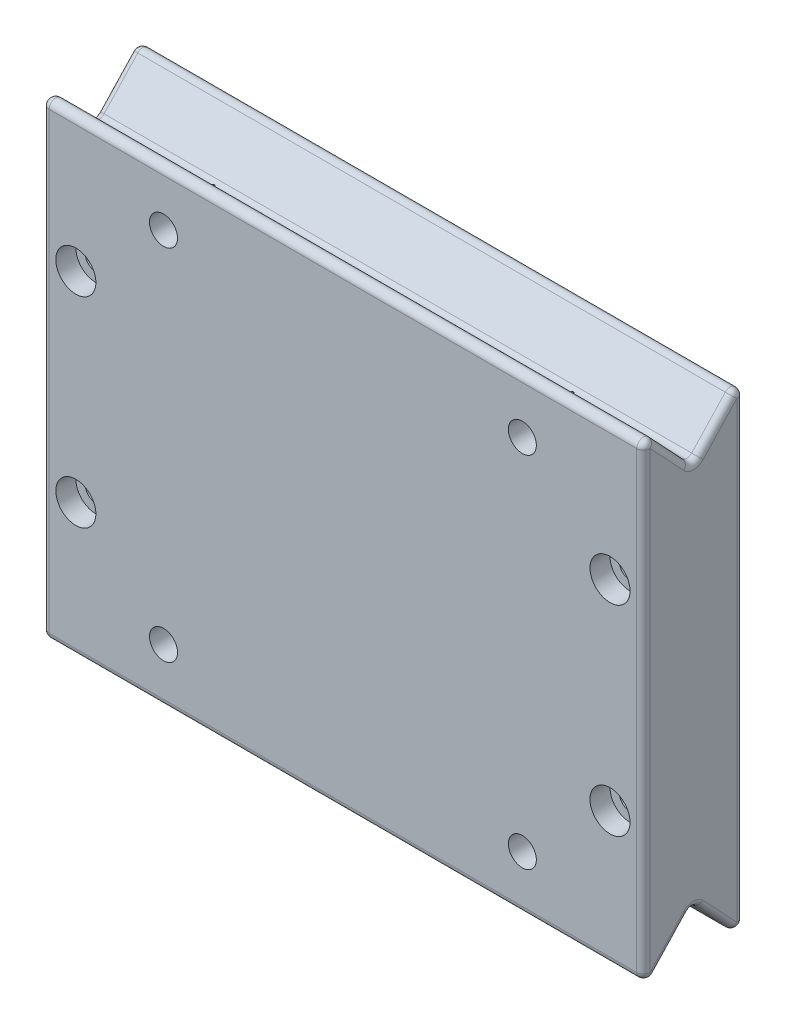
SolidWorks part; units mm, degrees
ref_plane "前视基准面" through (0, 0, 0) normal (0, 0, 1) x (1, 0, 0)
ref_plane "上视基准面" through (0, 0, 0) normal (0, 1, 0) x (1, 0, 0)
ref_plane "右视基准面" through (0, 0, 0) normal (1, 0, 0) x (0, 0, -1)
other "Configuration Table"
sketch "草图1" plane through (0, 0, 0) normal (0, 0, 1) x (1, 0, 0)
  line L0 (0, 0) -> (0, 22500.8852) construction
  line L1 (0, 0) -> (22500.8852, 0) construction
  line L3 (-45, 36.5) -> (45, 36.5)
  line L4 (-45, 36.5) -> (-45, -36.5)
  line L5 (-45, -36.5) -> (45, -36.5)
  line L6 (45, 36.5) -> (45, -36.5)
  line L7 (-45, 36.5) -> (45, -36.5) construction
  line L8 (-45, -36.5) -> (45, 36.5) construction
  circle A0 centre (-26.87, 26.87) radius 2.1
  circle A1 centre (26.87, 26.87) radius 2.1
  circle A2 centre (26.87, -26.87) radius 2.1
  circle A3 centre (-26.87, -26.87) radius 2.1
  point P5 (0, 0)
  dimension "D3" = 53.74
  dimension "D4" = 53.74
  dimension "D5" = 4.2
  dimension "D1" = 90
  dimension "D2" = 73
extrude "凸台-拉伸1" add sketch "草图1" along normal blind 15
sketch "草图2" plane through (0, 0, 0) normal (0, 0, -1) x (-1, 0, 0)
  line L0 (0, 36.5) -> (0, -36.5) construction
  line L1 (45, 36.5) -> (-45, 36.5) construction
  line L2 (45, -36.5) -> (-45, -36.5) construction
  line L3 (-45, 0) -> (45, 0) construction
  line L4 (-45, 36.5) -> (-45, -36.5) construction
  line L5 (45, 36.5) -> (45, -36.5) construction
  circle A0 centre (-26.87, 26.87) radius 4.5
  circle A1 centre (26.87, 26.87) radius 4.5
  circle A2 centre (26.87, -26.87) radius 4.5
  circle A3 centre (-26.87, -26.87) radius 4.5
  dimension "D1" = 9
extrude "切除-拉伸1" cut sketch "草图2" against normal blind 3
sketch "草图5" plane through (-45, 0, 0) normal (-1, 0, 0) x (0, 0, 1)
  line L0 (0, 0) -> (15, 0) construction
  line L1 (15, 36.5) -> (15, -36.5) construction
  line L2 (7.5, 36.5) -> (7.5, -36.5) construction
  line L3 (15, 36.5) -> (0, 36.5) construction
  line L4 (15, -36.5) -> (0, -36.5) construction
  line L5 (0, 36.5) -> (7.5, 28.5)
  line L7 (15, 36.5) -> (0, 36.5)
  line L8 (0, -36.5) -> (7.5, -28.5)
  line L9 (7.5, -28.5) -> (15, -36.5)
  line L10 (15, -36.5) -> (0, -36.5)
  line L11 (7.5, 28.5) -> (15, 36.5)
  dimension "D1" = 8
  dimension "D2" = 8
extrude "切除-拉伸4" cut sketch "草图5" against normal through all
sketch "草图6" plane through (0, 0, 15) normal (0, 0, 1) x (1, 0, 0)
  line L0 (0, 0) -> (-50000, 0) construction
  line L1 (0, 0) -> (0, 50000) construction
  line L2 (-45, 36.5) -> (-45, -36.5) construction
  circle A0 centre (-40, 15) radius 1.6
  circle A1 centre (-40, -15) radius 1.6
  circle A2 centre (40, -15) radius 1.6
  circle A3 centre (40, 15) radius 1.6
  dimension "D1" = 15
  dimension "D2" = 5
  dimension "D3" = 3.2
extrude "切除-拉伸5" cut sketch "草图6" against normal through all
sketch "草图7" plane through (0, 0, 15) normal (0, 0, 1) x (1, 0, 0)
  line L0 (0, 36.5) -> (0, -36.5) construction
  line L1 (45, 36.5) -> (-45, 36.5) construction
  line L2 (-45, -36.5) -> (45, -36.5) construction
  line L3 (-45, 0) -> (45, 0) construction
  line L4 (-45, 36.5) -> (-45, -36.5) construction
  line L5 (45, -36.5) -> (45, 36.5) construction
  circle A0 centre (-40, 15) radius 3
  circle A1 centre (-40, -15) radius 3
  circle A2 centre (40, -15) radius 3
  circle A3 centre (40, 15) radius 3
  dimension "D1" = 6
extrude "切除-拉伸6" cut sketch "草图7" against normal blind 3
fillet "圆角5" radius 1 4 edges at (0, -36.5, 0) (0, -36.5, 15) (-36.597, -28.5, 7.5) (36.597, -28.5, 7.5)
fillet "圆角6" radius 1 4 edges at (0, 36.5, 0) (-36.597, 28.5, 7.5) (36.597, 28.5, 7.5) (0, 36.5, 15)
fillet "圆角7" radius 1 12 edges at (45, 34.9011, 0.6323) (45, -34.9011, 0.6323) (45, -28.9621, 7.5) (45, -34.9011, 14.3677) (45, 34.9011, 14.3677) (45, 28.9621, 7.5) (45, -31.9667, 4.25) (45, -31.9667, 10.75) (45, 0, 0) (45, 0, 15) (45, 31.9667, 10.75) (45, 31.9667, 4.25)
fillet "圆角8" radius 1 12 edges at (-45, 34.9011, 14.3677) (-45, 28.9621, 7.5) (-45, 34.9011, 0.6323) (-45, -34.9011, 0.6323) (-45, -28.9621, 7.5) (-45, -34.9011, 14.3677) (-45, -31.9667, 4.25) (-45, -31.9667, 10.75) (-45, 31.9667, 4.25) (-45, 31.9667, 10.75) (-45, 0, 0) (-45, 0, 15)
